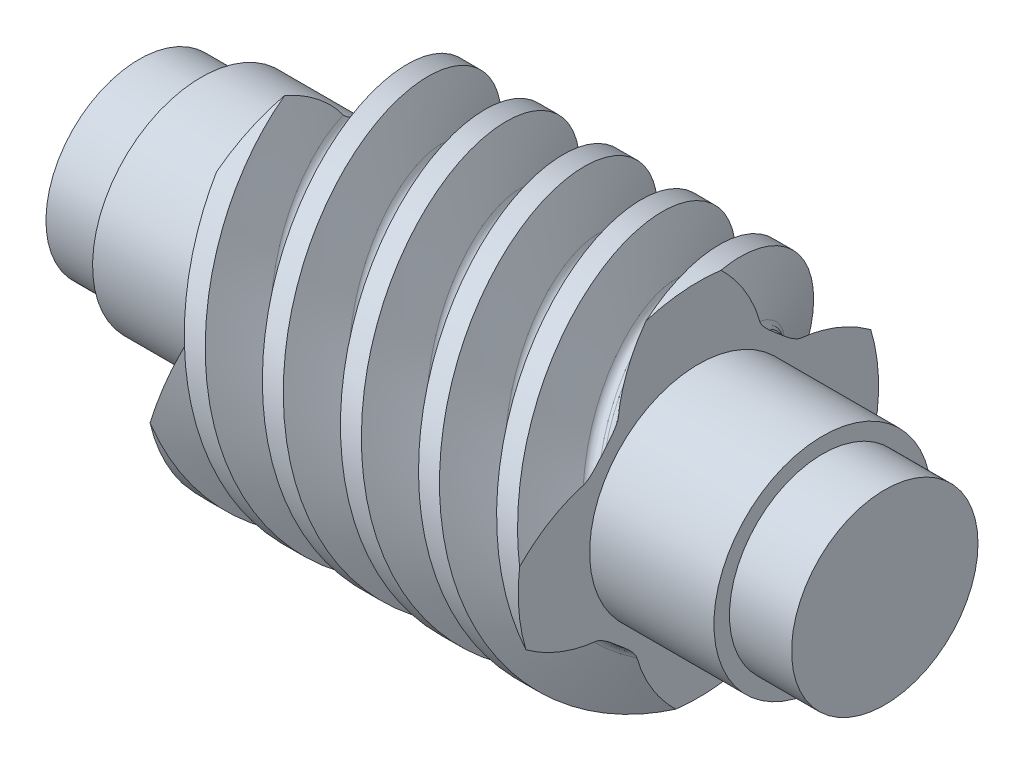
SolidWorks part; units mm, degrees
note: '?' marks a value the reader was unsure of.
ref_plane "前视基准面" through (0, 0, 0) normal (0, 0, 1) x (1, 0, 0)
ref_plane "上视基准面" through (0, 0, 0) normal (0, 1, 0) x (1, 0, 0)
ref_plane "右视基准面" through (0, 0, 0) normal (1, 0, 0) x (0, 0, -1)
ref_axis "基准轴1" through (-10.9638, 0, 0) along (1, 0, 0)?
sketch "草图1" plane through (0, 0, 0) normal (0, 0, 1) x (1, 0, 0)
  line L0 (-56.8494, 0) -> (118.6822, 0) construction
  line L1 (0, 48.1623) -> (0, -71.9241) construction
  line L2 (0, 11.6) -> (0, 0)
  line L3 (-10.9638, 0) -> (40.5935, 0) construction
  line L7 (0, 11.6) -> (24.48, 11.6)
  line L13 (0, 0) -> (24.48, 0)
  line L14 (24.48, 0) -> (24.48, 11.6)
  dimension "da1" = 11.6
  dimension "B1" = 24.48
revolve "旋转1" add sketch "草图1" angle 360 about L0
sketch "草图2" plane through (0, 0, 0) normal (1, 0, 0) x (0, 0, -1)
  circle A0 centre (0, 0) radius 10
  dimension "d1" = 20
sketch "草图3" plane through (0, 0, 0) normal (0, 0, 1) x (1, 0, 0)
  line L0 (0, 25.9401) -> (0, 0) construction
  line L1 (-5.517, 11.6) -> (-1.839, 11.6)
  line L2 (0, 11.6) -> (24.48, 11.6) construction
  line L3 (-1.839, 11.6) -> (-3.0037, 8.4001)
  line L4 (-3.575, 8) -> (-3.7809, 8)
  line L5 (-3.678, 11.6) -> (-3.678, 8) construction
  line L6 (0, 0) -> (8.7963, 0) construction
  line L7 (-4.9346, 10) -> (-2.4213, 10) construction
  line L8 (-4.3523, 8.4001) -> (-5.517, 11.6)
  line L9 (-5.517, 11.6) -> (-5.517, -8.4) construction
  line L10 (-3.678, 11.6) -> (0, 11.6) construction
  arc A0 (-4.3523, 8.4001) -> (-3.7809, 8) centre (-3.7809, 8.608) ccw
  arc A1 (-3.575, 8) -> (-3.0037, 8.4001) centre (-3.575, 8.608) ccw
  point P14 (-4.2067, 8)
  point P19 (-3.1493, 8)
  dimension "ppn" = 0.608
  dimension "df1" = 16
  dimension "d1" = 20
  dimension "0.5px" = 2.5133
  dimension "aa1" = 20
  dimension "aa" = 20
sketch "草图4" plane through (0, 0, 0) normal (1, 0, 0) x (0, 0, -1)
  circle A0 centre (0, 0) radius 8
sketch "草图5" plane through (24.48, 0, 0) normal (1, 0, 0) x (0, 0, -1)
  circle A0 centre (0, 0) radius 8 construction
  circle A1 centre (0, 0) radius 8
curve "螺旋线/涡状线1" pitch 20.1062 height 48.96 turns 2.4351
sweep "切除-扫描1" cut profiles "草图3" path "螺旋线/涡状线1" align with end faces yes
pattern_circular "阵列(圆周)1" count 4 every 90 about axis through (-10.9638, 0, 0) along (1, 0, 0) of "切除-扫描1"
extrude "凸台-拉伸1" add sketch "草图4" against normal blind 12.24
extrude "凸台-拉伸2" add sketch "草图5" along normal blind 12.24
sketch "草图6" plane through (-12.24, 0, 0) normal (-1, 0, 0) x (0, 0, 1)
  line L0 (-1.533, 2.1) -> (1.533, 2.1)
  arc A0 (-1.533, 2.1) -> (1.533, 2.1) centre (0, 0) ccw
  dimension "D1" = 5.2
  dimension "D2" = 2.1
extrude "切除-拉伸1" cut sketch "草图6" against normal blind 30
sketch "草图8" plane through (0, 0, 0) normal (0, 0, 1) x (1, 0, 0)
  line L0 (36.72, -8) -> (36.72, 8) construction
  line L1 (-11.76, 12.2583) -> (36.24, 12.2583)
  line L2 (-11.76, 12.2583) -> (-11.76, -14.4545)
  line L3 (-11.76, -14.4545) -> (36.24, -14.4545)
  line L4 (36.24, 12.2583) -> (36.24, -14.4545)
  dimension "D1" = 48
  dimension "D2" = 0.48
extrude "切除-拉伸2" cut sketch "草图8" against normal through all both and the other way through all flip side to cut
sketch "草图9" plane through (36.24, 0, 0) normal (1, 0, 0) x (0, 0, -1)
  circle A0 centre (0, 0) radius 9.4223
  circle A1 centre (0, 0) radius 6
  dimension "D1" = 12
extrude "切除-拉伸4" cut sketch "草图9" against normal blind 4
sketch "草图10" plane through (32.24, 0, 0) normal (1, 0, 0) x (0, 0, -1)
  circle A0 centre (0, 0) radius 7
  circle A1 centre (0, 0) radius 13.1077
  dimension "D1" = 14
extrude "切除-拉伸5" cut sketch "草图10" against normal blind 8
sketch "草图11" plane through (-11.76, 0, 0) normal (-1, 0, 0) x (0, 0, 1)
  circle A0 centre (0, 0) radius 6
  circle A1 centre (0, 0) radius 7
  dimension "D1" = 12
  dimension "D2" = 14
extrude "切除-拉伸6" cut sketch "草图11" against normal blind 4
sketch "草图12" plane through (-11.76, 0, 0) normal (-1, 0, 0) x (0, 0, 1)
  circle A0 centre (0, 0) radius 13.748
  circle A1 centre (0, 0) radius 7
  dimension "D1" = 14
extrude "切除-拉伸7" cut sketch "草图12" against normal blind 12
